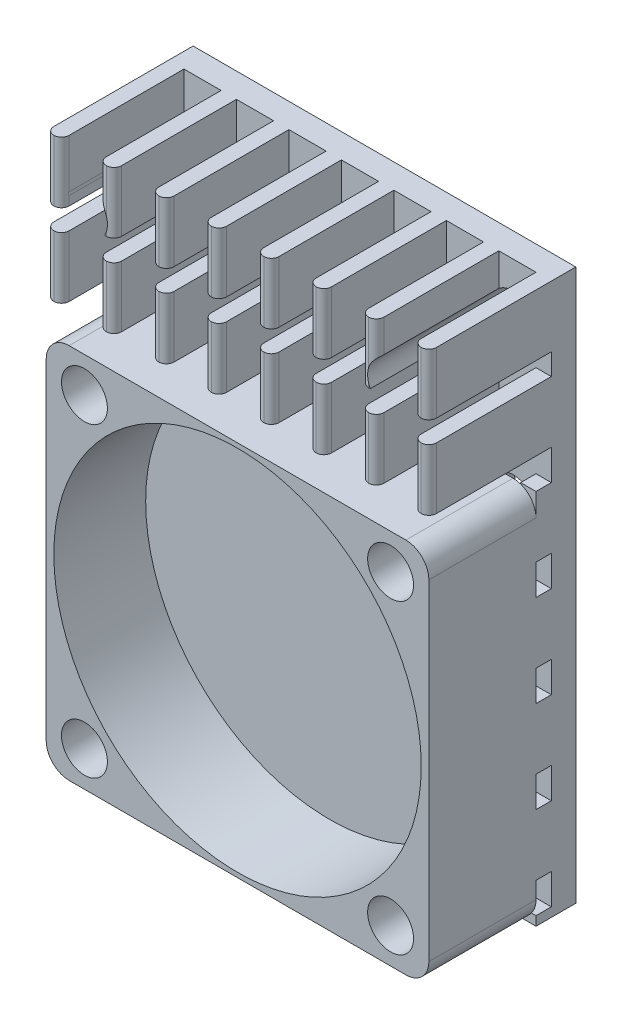
SolidWorks part; units mm, degrees
ref_plane "Front Plane" through (0, 0, 0) normal (0, 0, 1) x (1, 0, 0)
ref_plane "Top Plane" through (0, 0, 0) normal (0, 1, 0) x (1, 0, 0)
ref_plane "Right Plane" through (0, 0, 0) normal (1, 0, 0) x (0, 0, -1)
sketch "Sketch1" plane through (0, 0, 0) normal (0, 0, 1) x (1, 0, 0)
  line L1 (12.5, -18) -> (-12.5, -18)
  line L2 (12.5, -18) -> (12.5, 18)
  line L3 (12.5, 18) -> (-12.5, 18)
  line L4 (-12.5, -18) -> (-12.5, 18)
  line L5 (12.5, -18) -> (-12.5, 18) construction
  line L6 (12.5, 18) -> (-12.5, -18) construction
  point P0 (0, 0)
  dimension "D1" = 36
  dimension "D2" = 25
extrude "Boss-Extrude1" add sketch "Sketch1" along normal blind 1.6
sketch "Sketch2" plane through (0, 0, 1.6) normal (0, 0, 1) x (1, 0, 0)
  line L0 (9.072, 18) -> (8.072, 18)
  line L1 (12.5, 18) -> (11.5, 18)
  line L2 (12.5, 18) -> (12.5, 14)
  line L3 (12.5, 14) -> (11.5, 14)
  line L4 (11.5, 18) -> (11.5, 14)
  line L5 (9.072, 18) -> (9.072, 14)
  line L6 (9.072, 14) -> (8.072, 14)
  line L7 (8.072, 18) -> (8.072, 14)
  line L8 (5.644, 18) -> (4.644, 18)
  line L9 (5.644, 18) -> (5.644, 14)
  line L10 (5.644, 14) -> (4.644, 14)
  line L11 (4.644, 18) -> (4.644, 14)
  line L12 (2.216, 18) -> (1.216, 18)
  line L13 (2.216, 18) -> (2.216, 14)
  line L14 (2.216, 14) -> (1.216, 14)
  line L15 (1.216, 18) -> (1.216, 14)
  line L16 (-1.212, 18) -> (-2.212, 18)
  line L17 (-1.212, 18) -> (-1.212, 14)
  line L18 (-1.212, 14) -> (-2.212, 14)
  line L19 (-2.212, 18) -> (-2.212, 14)
  line L20 (-4.64, 18) -> (-5.64, 18)
  line L21 (-4.64, 18) -> (-4.64, 14)
  line L22 (-4.64, 14) -> (-5.64, 14)
  line L23 (-5.64, 18) -> (-5.64, 14)
  line L24 (-8.068, 18) -> (-9.068, 18)
  line L25 (-8.068, 18) -> (-8.068, 14)
  line L26 (-8.068, 14) -> (-9.068, 14)
  line L27 (-9.068, 18) -> (-9.068, 14)
  line L28 (-11.496, 18) -> (-12.496, 18)
  line L29 (-11.496, 18) -> (-11.496, 14)
  line L30 (-11.496, 14) -> (-12.496, 14)
  line L31 (-12.496, 18) -> (-12.496, 14)
  line L32 (-12.496, 12.6) -> (-12.496, 8.6)
  line L33 (-11.496, 12.6) -> (-12.496, 12.6)
  line L34 (-11.496, 12.6) -> (-11.496, 8.6)
  line L35 (-11.496, 8.6) -> (-12.496, 8.6)
  line L36 (-8.068, 12.6) -> (-9.068, 12.6)
  line L37 (-9.068, 12.6) -> (-9.068, 8.6)
  line L38 (-8.068, 8.6) -> (-9.068, 8.6)
  line L39 (-8.068, 12.6) -> (-8.068, 8.6)
  line L40 (-4.64, 12.6) -> (-5.64, 12.6)
  line L41 (-5.64, 12.6) -> (-5.64, 8.6)
  line L42 (-4.64, 8.6) -> (-5.64, 8.6)
  line L43 (-4.64, 12.6) -> (-4.64, 8.6)
  line L44 (-1.212, 12.6) -> (-2.212, 12.6)
  line L45 (-2.212, 12.6) -> (-2.212, 8.6)
  line L46 (-1.212, 8.6) -> (-2.212, 8.6)
  line L47 (-1.212, 12.6) -> (-1.212, 8.6)
  line L48 (2.216, 12.6) -> (1.216, 12.6)
  line L49 (1.216, 12.6) -> (1.216, 8.6)
  line L50 (2.216, 8.6) -> (1.216, 8.6)
  line L51 (2.216, 12.6) -> (2.216, 8.6)
  line L52 (5.644, 12.6) -> (4.644, 12.6)
  line L53 (4.644, 12.6) -> (4.644, 8.6)
  line L54 (5.644, 8.6) -> (4.644, 8.6)
  line L55 (5.644, 12.6) -> (5.644, 8.6)
  line L56 (9.072, 12.6) -> (8.072, 12.6)
  line L57 (8.072, 12.6) -> (8.072, 8.6)
  line L58 (9.072, 8.6) -> (8.072, 8.6)
  line L59 (9.072, 12.6) -> (9.072, 8.6)
  line L60 (12.5, 12.6) -> (11.5, 12.6)
  line L61 (11.5, 12.6) -> (11.5, 8.6)
  line L62 (12.5, 8.6) -> (11.5, 8.6)
  line L63 (12.5, 12.6) -> (12.5, 8.6)
  dimension "D1" = 4
  dimension "D2" = 1
  dimension "D3" = 8
  dimension "D4" = 2
extrude "Boss-Extrude2" add sketch "Sketch2" along normal blind 8
fillet "Fillet1" radius 0.5 32 edges at (-12.496, 16, 9.6) (-11.496, 16, 9.6) (-12.496, 10.6, 9.6) (-11.496, 10.6, 9.6) (-9.068, 16, 9.6) (-8.068, 16, 9.6) (-9.068, 10.6, 9.6) (-8.068, 10.6, 9.6) (-5.64, 16, 9.6) (-4.64, 16, 9.6) (-5.64, 10.6, 9.6) (-4.64, 10.6, 9.6) (-2.212, 16, 9.6) (-1.212, 16, 9.6) (-2.212, 10.6, 9.6) (-1.212, 10.6, 9.6) (1.216, 16, 9.6) (2.216, 16, 9.6) (1.216, 10.6, 9.6) (2.216, 10.6, 9.6) (4.644, 16, 9.6) (5.644, 16, 9.6) (4.644, 10.6, 9.6) (5.644, 10.6, 9.6) (8.072, 16, 9.6) (9.072, 16, 9.6) (8.072, 10.6, 9.6) (9.072, 10.6, 9.6) (12.5, 10.6, 9.6) (11.5, 10.6, 9.6) (11.5, 16, 9.6) (12.5, 16, 9.6)
sketch "Sketch3" plane through (0, 0, 1.6) normal (0, 0, 1) x (1, 0, 0)
  line L0 (-12.4983, 6.6) -> (12.5, 6.6)
  line L1 (-12.5, -18) -> (12.5, -18) construction
  line L6 (-12.5, -18) -> (12.5, -18)
  line L7 (-12.5, -18) -> (-11.496, -18)
  line L8 (-12.496, 2.6) -> (-12.496, 6.6)
  line L9 (-11.496, 6.6) -> (-12.4983, 6.6)
  line L10 (-11.496, 2.6) -> (-11.496, 6.6)
  line L11 (-12.4983, 2.6) -> (-11.496, 2.6)
  line L12 (-12.496, -3.4) -> (-12.496, 0.6)
  line L13 (-11.496, 0.6) -> (-12.4983, 0.6)
  line L14 (-11.496, -3.4) -> (-11.496, 0.6)
  line L15 (-12.4983, -3.4) -> (-11.496, -3.4)
  line L16 (-12.496, -9.4) -> (-12.496, -5.4)
  line L17 (-11.496, -5.4) -> (-12.4983, -5.4)
  line L18 (-11.496, -9.4) -> (-11.496, -5.4)
  line L19 (-12.4983, -9.4) -> (-11.496, -9.4)
  line L20 (-12.496, -15.4) -> (-12.496, -11.4)
  line L21 (-11.496, -11.4) -> (-12.4983, -11.4)
  line L22 (-11.496, -15.4) -> (-11.496, -11.4)
  line L23 (-12.4983, -15.4) -> (-11.496, -15.4)
  line L24 (-12.496, -18) -> (-12.496, -17.4)
  line L25 (-11.496, -17.4) -> (-12.4983, -17.4)
  line L26 (-11.496, -18) -> (-11.496, -17.4)
  line L27 (-9.068, -18) -> (-8.068, -18)
  line L28 (-9.068, 2.6) -> (-9.068, 6.6)
  line L29 (-8.068, 6.6) -> (-9.0703, 6.6)
  line L30 (-8.068, 2.6) -> (-8.068, 6.6)
  line L31 (-9.0703, 2.6) -> (-8.068, 2.6)
  line L32 (-9.068, -3.4) -> (-9.068, 0.6)
  line L33 (-8.068, 0.6) -> (-9.0703, 0.6)
  line L34 (-8.068, -3.4) -> (-8.068, 0.6)
  line L35 (-9.0703, -3.4) -> (-8.068, -3.4)
  line L36 (-9.068, -9.4) -> (-9.068, -5.4)
  line L37 (-8.068, -5.4) -> (-9.0703, -5.4)
  line L38 (-8.068, -9.4) -> (-8.068, -5.4)
  line L39 (-9.0703, -9.4) -> (-8.068, -9.4)
  line L40 (-9.068, -15.4) -> (-9.068, -11.4)
  line L41 (-8.068, -11.4) -> (-9.0703, -11.4)
  line L42 (-8.068, -15.4) -> (-8.068, -11.4)
  line L43 (-9.0703, -15.4) -> (-8.068, -15.4)
  line L44 (-9.068, -18) -> (-9.068, -17.4)
  line L45 (-8.068, -17.4) -> (-9.0703, -17.4)
  line L46 (-8.068, -18) -> (-8.068, -17.4)
  line L47 (-5.64, -18) -> (-4.64, -18)
  line L48 (-5.64, 2.6) -> (-5.64, 6.6)
  line L49 (-4.64, 6.6) -> (-5.6423, 6.6)
  line L50 (-4.64, 2.6) -> (-4.64, 6.6)
  line L51 (-5.6423, 2.6) -> (-4.64, 2.6)
  line L52 (-5.64, -3.4) -> (-5.64, 0.6)
  line L53 (-4.64, 0.6) -> (-5.6423, 0.6)
  line L54 (-4.64, -3.4) -> (-4.64, 0.6)
  line L55 (-5.6423, -3.4) -> (-4.64, -3.4)
  line L56 (-5.64, -9.4) -> (-5.64, -5.4)
  line L57 (-4.64, -5.4) -> (-5.6423, -5.4)
  line L58 (-4.64, -9.4) -> (-4.64, -5.4)
  line L59 (-5.6423, -9.4) -> (-4.64, -9.4)
  line L60 (-5.64, -15.4) -> (-5.64, -11.4)
  line L61 (-4.64, -11.4) -> (-5.6423, -11.4)
  line L62 (-4.64, -15.4) -> (-4.64, -11.4)
  line L63 (-5.6423, -15.4) -> (-4.64, -15.4)
  line L64 (-5.64, -18) -> (-5.64, -17.4)
  line L65 (-4.64, -17.4) -> (-5.6423, -17.4)
  line L66 (-4.64, -18) -> (-4.64, -17.4)
  line L67 (-2.212, -18) -> (-1.212, -18)
  line L68 (-2.212, 2.6) -> (-2.212, 6.6)
  line L69 (-1.212, 6.6) -> (-2.2143, 6.6)
  line L70 (-1.212, 2.6) -> (-1.212, 6.6)
  line L71 (-2.2143, 2.6) -> (-1.212, 2.6)
  line L72 (-2.212, -3.4) -> (-2.212, 0.6)
  line L73 (-1.212, 0.6) -> (-2.2143, 0.6)
  line L74 (-1.212, -3.4) -> (-1.212, 0.6)
  line L75 (-2.2143, -3.4) -> (-1.212, -3.4)
  line L76 (-2.212, -9.4) -> (-2.212, -5.4)
  line L77 (-1.212, -5.4) -> (-2.2143, -5.4)
  line L78 (-1.212, -9.4) -> (-1.212, -5.4)
  line L79 (-2.2143, -9.4) -> (-1.212, -9.4)
  line L80 (-2.212, -15.4) -> (-2.212, -11.4)
  line L81 (-1.212, -11.4) -> (-2.2143, -11.4)
  line L82 (-1.212, -15.4) -> (-1.212, -11.4)
  line L83 (-2.2143, -15.4) -> (-1.212, -15.4)
  line L84 (-2.212, -18) -> (-2.212, -17.4)
  line L85 (-1.212, -17.4) -> (-2.2143, -17.4)
  line L86 (-1.212, -18) -> (-1.212, -17.4)
  line L87 (1.216, -18) -> (2.216, -18)
  line L88 (1.216, 2.6) -> (1.216, 6.6)
  line L89 (2.216, 6.6) -> (1.2137, 6.6)
  line L90 (2.216, 2.6) -> (2.216, 6.6)
  line L91 (1.2137, 2.6) -> (2.216, 2.6)
  line L92 (1.216, -3.4) -> (1.216, 0.6)
  line L93 (2.216, 0.6) -> (1.2137, 0.6)
  line L94 (2.216, -3.4) -> (2.216, 0.6)
  line L95 (1.2137, -3.4) -> (2.216, -3.4)
  line L96 (1.216, -9.4) -> (1.216, -5.4)
  line L97 (2.216, -5.4) -> (1.2137, -5.4)
  line L98 (2.216, -9.4) -> (2.216, -5.4)
  line L99 (1.2137, -9.4) -> (2.216, -9.4)
  line L100 (1.216, -15.4) -> (1.216, -11.4)
  line L101 (2.216, -11.4) -> (1.2137, -11.4)
  line L102 (2.216, -15.4) -> (2.216, -11.4)
  line L103 (1.2137, -15.4) -> (2.216, -15.4)
  line L104 (1.216, -18) -> (1.216, -17.4)
  line L105 (2.216, -17.4) -> (1.2137, -17.4)
  line L106 (2.216, -18) -> (2.216, -17.4)
  line L107 (4.644, -18) -> (5.644, -18)
  line L108 (4.644, 2.6) -> (4.644, 6.6)
  line L109 (5.644, 6.6) -> (4.6417, 6.6)
  line L110 (5.644, 2.6) -> (5.644, 6.6)
  line L111 (4.6417, 2.6) -> (5.644, 2.6)
  line L112 (4.644, -3.4) -> (4.644, 0.6)
  line L113 (5.644, 0.6) -> (4.6417, 0.6)
  line L114 (5.644, -3.4) -> (5.644, 0.6)
  line L115 (4.6417, -3.4) -> (5.644, -3.4)
  line L116 (4.644, -9.4) -> (4.644, -5.4)
  line L117 (5.644, -5.4) -> (4.6417, -5.4)
  line L118 (5.644, -9.4) -> (5.644, -5.4)
  line L119 (4.6417, -9.4) -> (5.644, -9.4)
  line L120 (4.644, -15.4) -> (4.644, -11.4)
  line L121 (5.644, -11.4) -> (4.6417, -11.4)
  line L122 (5.644, -15.4) -> (5.644, -11.4)
  line L123 (4.6417, -15.4) -> (5.644, -15.4)
  line L124 (4.644, -18) -> (4.644, -17.4)
  line L125 (5.644, -17.4) -> (4.6417, -17.4)
  line L126 (5.644, -18) -> (5.644, -17.4)
  line L127 (8.072, -18) -> (9.072, -18)
  line L128 (8.072, 2.6) -> (8.072, 6.6)
  line L129 (9.072, 6.6) -> (8.0697, 6.6)
  line L130 (9.072, 2.6) -> (9.072, 6.6)
  line L131 (8.0697, 2.6) -> (9.072, 2.6)
  line L132 (8.072, -3.4) -> (8.072, 0.6)
  line L133 (9.072, 0.6) -> (8.0697, 0.6)
  line L134 (9.072, -3.4) -> (9.072, 0.6)
  line L135 (8.0697, -3.4) -> (9.072, -3.4)
  line L136 (8.072, -9.4) -> (8.072, -5.4)
  line L137 (9.072, -5.4) -> (8.0697, -5.4)
  line L138 (9.072, -9.4) -> (9.072, -5.4)
  line L139 (8.0697, -9.4) -> (9.072, -9.4)
  line L140 (8.072, -15.4) -> (8.072, -11.4)
  line L141 (9.072, -11.4) -> (8.0697, -11.4)
  line L142 (9.072, -15.4) -> (9.072, -11.4)
  line L143 (8.0697, -15.4) -> (9.072, -15.4)
  line L144 (8.072, -18) -> (8.072, -17.4)
  line L145 (9.072, -17.4) -> (8.0697, -17.4)
  line L146 (9.072, -18) -> (9.072, -17.4)
  line L147 (11.5, -18) -> (12.5, -18)
  line L148 (11.5, 2.6) -> (11.5, 6.6)
  line L149 (12.5, 6.6) -> (11.4977, 6.6)
  line L150 (12.5, 2.6) -> (12.5, 6.6)
  line L151 (11.4977, 2.6) -> (12.5, 2.6)
  line L152 (11.5, -3.4) -> (11.5, 0.6)
  line L153 (12.5, 0.6) -> (11.4977, 0.6)
  line L154 (12.5, -3.4) -> (12.5, 0.6)
  line L155 (11.4977, -3.4) -> (12.5, -3.4)
  line L156 (11.5, -9.4) -> (11.5, -5.4)
  line L157 (12.5, -5.4) -> (11.4977, -5.4)
  line L158 (12.5, -9.4) -> (12.5, -5.4)
  line L159 (11.4977, -9.4) -> (12.5, -9.4)
  line L160 (11.5, -15.4) -> (11.5, -11.4)
  line L161 (12.5, -11.4) -> (11.4977, -11.4)
  line L162 (12.5, -15.4) -> (12.5, -11.4)
  line L163 (11.4977, -15.4) -> (12.5, -15.4)
  line L164 (11.5, -18) -> (11.5, -17.4)
  line L165 (12.5, -17.4) -> (11.4977, -17.4)
  line L166 (12.5, -18) -> (12.5, -17.4)
extrude "Boss-Extrude3" add sketch "Sketch3" along normal blind 1 contours L8 L11 L10 L0 | L28 L31 L30 L0 | L48 L51 L50 L0 | L68 L71 L70 L0 | L88 L91 L90 L0 | L108 L111 L110 L0 | L128 L131 L130 L0 | L148 L151 L150 L0 | L12 L15 L14 L13 | L32 L35 L34 L33 | L52 L55 L54 L53 | L72 L75 L74 L73 | L92 L95 L94 L93 | L112 L115 L114 L113 | L132 L135 L134 L133 | L152 L155 L154 L153 | L156 L159 L158 L157 | L136 L139 L138 L137 | L116 L119 L118 L117 | L96 L99 L98 L97 | L76 L79 L78 L77 | L56 L59 L58 L57 | L36 L39 L38 L37 | L16 L19 L18 L17 | L20 L23 L22 L21 | L40 L43 L42 L41 | L60 L63 L62 L61 | L80 L83 L82 L81 | L100 L103 L102 L101 | L120 L123 L122 L121 | L140 L143 L142 L141 | L160 L163 L162 L161 | L6 L166 L165 L164 | L6 L146 L145 L144 | L6 L126 L125 L124 | L6 L106 L105 L104 | L6 L86 L85 L84 | L6 L66 L65 L64 | L6 L46 L45 L44 | L7 L26 L25 L24 region at (12, 4.6, 1.6) region at (8.572, 4.6, 1.6) region at (5.144, 4.6, 1.6) region at (1.716, 4.6, 1.6) region at (-1.712, 4.6, 1.6) region at (-5.14, 4.6, 1.6) region at (-8.568, 4.6, 1.6) region at (-11.996, 4.6, 1.6) region at (-11.996, -17.7, 1.6) region at (12, -17.7, 1.6) region at (8.572, -17.7, 1.6) region at (5.144, -17.7, 1.6) region at (1.716, -17.7, 1.6) region at (-1.712, -17.7, 1.6) region at (-5.14, -17.7, 1.6) region at (-8.568, -17.7, 1.6) region at (-11.996, -1.4, 1.6) region at (-11.996, -7.4, 1.6) region at (-11.996, -13.4, 1.6) region at (-8.568, -1.4, 1.6) region at (-8.568, -7.4, 1.6) region at (-8.568, -13.4, 1.6) region at (-5.14, -1.4, 1.6) region at (-5.14, -7.4, 1.6) region at (-5.14, -13.4, 1.6) region at (-1.712, -1.4, 1.6) region at (-1.712, -7.4, 1.6) region at (-1.712, -13.4, 1.6) region at (1.716, -1.4, 1.6) region at (1.716, -7.4, 1.6) region at (1.716, -13.4, 1.6) region at (5.144, -1.4, 1.6) region at (5.144, -7.4, 1.6) region at (5.144, -13.4, 1.6) region at (8.572, -1.4, 1.6) region at (8.572, -7.4, 1.6) region at (8.572, -13.4, 1.6) region at (12, -1.4, 1.6) region at (12, -7.4, 1.6) region at (12, -13.4, 1.6)
sketch "Sketch5" plane through (0, 0, 2.6) normal (0, 0, 1) x (1, 0, 0)
  line L1 (-10.996, 6.6) -> (11, 6.6)
  line L2 (-12.496, 5.1) -> (-12.496, -16.5)
  line L3 (-10.996, -18) -> (11, -18)
  line L4 (12.5, 5.1) -> (12.5, -16.5)
  arc A0 (11, -18) -> (12.5, -16.5) centre (11, -16.5) ccw
  arc A1 (-12.496, -16.5) -> (-10.996, -18) centre (-10.996, -16.5) ccw
  arc A2 (11, 6.6) -> (12.5, 5.1) centre (11, 5.1) cw
  arc A3 (-10.996, 6.6) -> (-12.496, 5.1) centre (-10.996, 5.1) ccw
  point P8 (12.5, -18)
  point P15 (-12.496, 6.6)
  dimension "D1" = 1.5
extrude "Boss-Extrude4" add sketch "Sketch5" along normal blind 7
sketch "Sketch6" plane through (0, 0, 9.6) normal (0, 0, 1) x (1, 0, 0)
  line L0 (0.002, 6.6) -> (0.002, -18) construction
  line L1 (11, 6.6) -> (-10.996, 6.6) construction
  line L2 (-10.996, -18) -> (11, -18) construction
  circle A0 centre (0.002, -5.7) radius 12
extrude "Cut-Extrude1" cut sketch "Sketch6" against normal blind 6
sketch "Sketch7" plane through (0, 0, 9.6) normal (0, 0, 1) x (1, 0, 0)
  line L0 (-12.496, -5.7) -> (12.5, -5.7) construction
  line L1 (-12.496, 5.1) -> (-12.496, -16.5) construction
  line L2 (12.5, -16.5) -> (12.5, 5.1) construction
  line L3 (0.002, 6.6) -> (0.002, -18) construction
  line L4 (11, 6.6) -> (-10.996, 6.6) construction
  line L5 (-10.996, -18) -> (11, -18) construction
  circle A0 centre (-9.998, 4.3) radius 1.5
  circle A1 centre (10.002, 4.3) radius 1.5
  circle A2 centre (10.002, -15.7) radius 1.5
  circle A3 centre (-9.998, -15.7) radius 1.5
  dimension "D3" = 3
  dimension "D1" = 20
  dimension "D2" = 20
extrude "Cut-Extrude2" cut sketch "Sketch7" against normal through all
sketch "Sketch8" plane through (0, 0, 0) normal (0, 0, -1) x (-1, 0, 0)
  line L0 (0, 18) -> (0, -18) construction
  line L1 (-12.5, 18) -> (12.5, 18) construction
  line L2 (12.5, -18) -> (-12.5, -18) construction
  line L3 (-10.002, -15.7) -> (9.998, -15.7) construction
  circle A0 centre (-10, 14.7) radius 1.5
  circle A2 centre (10, 14.7) radius 1.5
  dimension "D2" = 3
  dimension "D1" = 20
  dimension "D3" = 30.4
extrude "Cut-Extrude3" cut sketch "Sketch8" against normal through all
